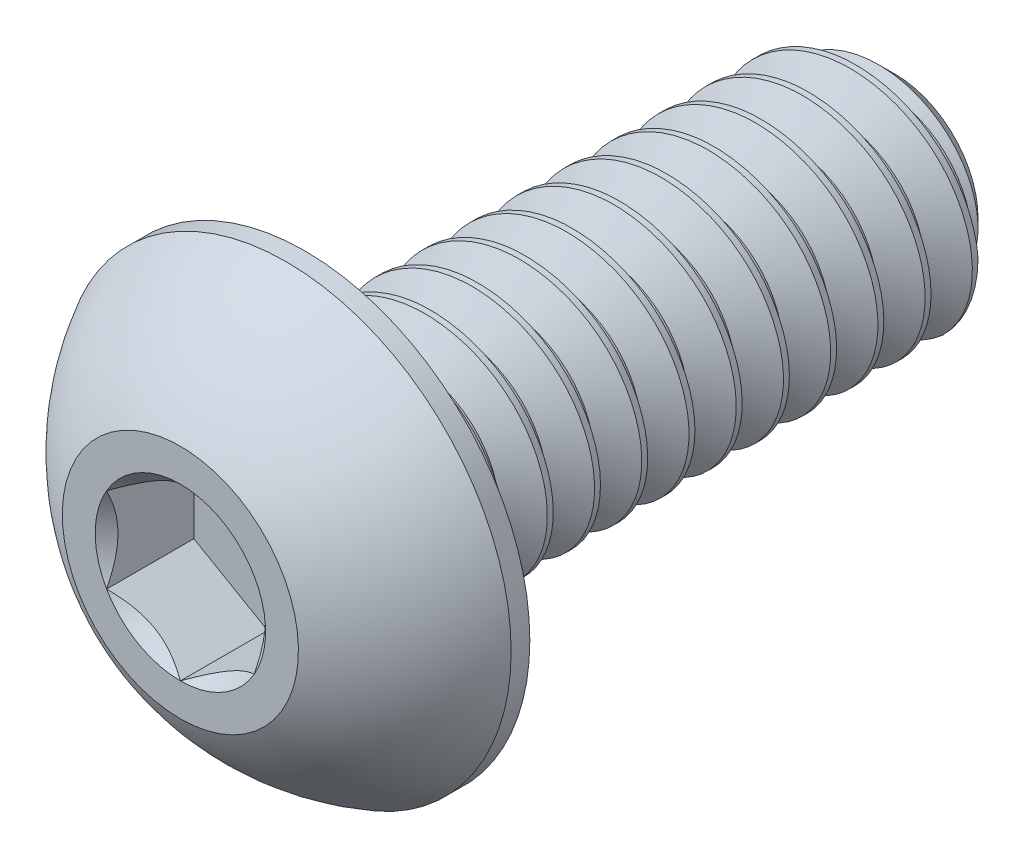
SolidWorks part; units mm, degrees
ref_plane "Front" through (0, 0, 0) normal (0, 0, 1) x (1, 0, 0)
ref_plane "Top" through (0, 0, 0) normal (0, 1, 0) x (1, 0, 0)
ref_plane "Right" through (0, 0, 0) normal (1, 0, 0) x (0, 0, -1)
sketch "Sketch1" plane through (0, 0, 0) normal (1, 0, 0) x (0, 0, -1)
  line L2 (1.6764, 1.5875) -> (9.6139, 1.5875)
  line L3 (9.6139, 1.5875) -> (9.6139, 0)
  line L4 (9.6139, 0) -> (1.6764, 0)
  line L6 (1.4249, 3.0226) -> (1.6764, 3.0226) construction
  line L7 (9.6139, 1.5875) -> (9.6139, -1.5875) construction
  line L8 (0, 0) -> (1.6764, 0) construction
  line L9 (1.6764, 3.0226) -> (1.6764, -3.0226) construction
  line L11 (1.6764, 1.5875) -> (1.6764, 0)
  line L13 (0, 0.9922) -> (0, -0.9922) construction
  line L14 (0, 0.9922) -> (0, 1.5875) construction
  arc A3 (0, 1.5875) -> (1.4249, 3.0226) centre (3.034, 0) cw construction
  dimension "D1" = 0.2515
  dimension "Head Ht" = 1.6764
  dimension "Head Dia" = 6.0452
  dimension "Dia" = 3.175
  dimension "Lg" = 7.9375
  dimension "Hex" = 1.9844
revolve "Revolve1" add sketch "Sketch1" angle 360 mid plane about L4
sketch "Sketch3" plane through (0, 0, -9.6139) normal (0, 0, -1) x (-1, 0, 0)
  circle A0 centre (0, 0) radius 1.5875
curve "Helix/Spiral1" pitch 0.635 height 8.5725 radius 1.5875 centre (0, 0, -9.6139) axis (0, 0, 1) start towards (0, 1, 0)
sketch "Sketch2" plane through (0, 0, 0) normal (1, 0, 0) x (0, 0, -1)
  line L0 (9.6139, 1.5875) -> (10.1695, 1.5875)
  line L1 (10.1695, 1.5875) -> (9.9314, 1.1751)
  line L2 (9.9314, 1.1751) -> (9.852, 1.1751)
  line L3 (9.852, 1.1751) -> (9.6139, 1.5875)
  line L4 (9.733, 1.3813) -> (10.0505, 1.3813) construction
  dimension "D1" = 60
  dimension "D2" = 0.0794
  dimension "D3" = 0.3175
chamfer "Chamfer1" distance 0.4763 angle 45 1 edges at (0, 1.5875, -9.6139)
sweep "Cut-Sweep1" cut profiles "Sketch2" path "Helix/Spiral1" align with end faces yes
sketch "Sketch7" plane through (0, 0, 0) normal (1, 0, 0) x (0, 0, -1)
  line L6 (1.4249, 3.0226) -> (1.6764, 3.0226) construction
  line L8 (0, 0) -> (1.6764, 0) construction
  line L11 (1.6764, 3.0226) -> (1.6764, -3.0226) construction
  line L12 (1.4249, 3.0226) -> (1.6764, 3.0226)
  line L13 (0, 0) -> (1.6764, 0)
  line L14 (0, 0.9922) -> (0, -0.9922) construction
  line L15 (1.6764, 3.0226) -> (1.6764, 0)
  line L16 (0, 1.5875) -> (0, 0)
  arc A2 (1.4249, 3.0226) -> (0, 1.5875) centre (3.034, 0) ccw construction
  arc A3 (1.4249, 3.0226) -> (0, 1.5875) centre (3.034, 0) ccw
revolve "Revolve2" add sketch "Sketch7" angle 360 mid plane about L13
sketch "Sketch5" plane through (0, 0, 0) normal (0, 0, 1) x (1, 0, 0)
  line L1 (0.9922, -0.5728) -> (0.9922, 0.5728)
  line L2 (0.9922, 0.5728) -> (0, 1.1457)
  line L3 (0, 1.1457) -> (-0.9922, 0.5728)
  line L4 (-0.9922, 0.5728) -> (-0.9922, -0.5728)
  line L5 (-0.9922, -0.5728) -> (0, -1.1457)
  line L6 (0, -1.1457) -> (0.9922, -0.5728)
  circle A0 centre (0, 0) radius 0.9922 construction
extrude "Cut-Extrude2" cut sketch "Sketch5" against normal blind 1.1735
sketch "Sketch6" plane through (0, 0, 0) normal (0, 0, 1) x (1, 0, 0)
  circle A0 centre (0, 0) radius 1.1457
extrude "Cut-Extrude3" cut sketch "Sketch6" against normal blind 1.1735 draft 45
sketch "Sketch9" [suppressed] plane through (0, 0, -1.4986) normal (0, 0, 1) x (1, 0, 0)
  circle A2 centre (0, 0) radius 1.4224
extrude "Boss-Extrude2" [suppressed] add sketch "Sketch9" against normal offset from surface (12.7 mm away) 31.75 up to face at (0, 1.1113, -9.6139)
sketch "Sketch10" plane through (0, 0, 0) normal (1, 0, 0) x (0, 0, -1)
  line L0 (9.6139, 1.5875) -> (9.6139, -1.5875) construction
  point P0 (8.6614, -1.5875)
  dimension "D1" = 0.9525
equation "\"D3@Helix/Spiral1\" = \"Lg@Sketch1\" + \"D4@Helix/Spiral1\""
equation "\"D2@Sketch2\" = \"D4@Helix/Spiral1\" * .125"
equation "\"D3@Sketch2\" = \"D4@Helix/Spiral1\" * .5"
equation "\"D1@Chamfer1\" = \"D4@Helix/Spiral1\" * .75"
equation "\"D1@Cut-Extrude2\" = \"Head Ht@Sketch1\" * .7"
equation "\"D1@Sketch1\" = \"Head Ht@Sketch1\" * .15"
equation "\"D1@Sketch10\" = \"D4@Helix/Spiral1\" * 1.5"
equation "\"D1@Cut-Extrude3\" = \"D1@Cut-Extrude2\""
